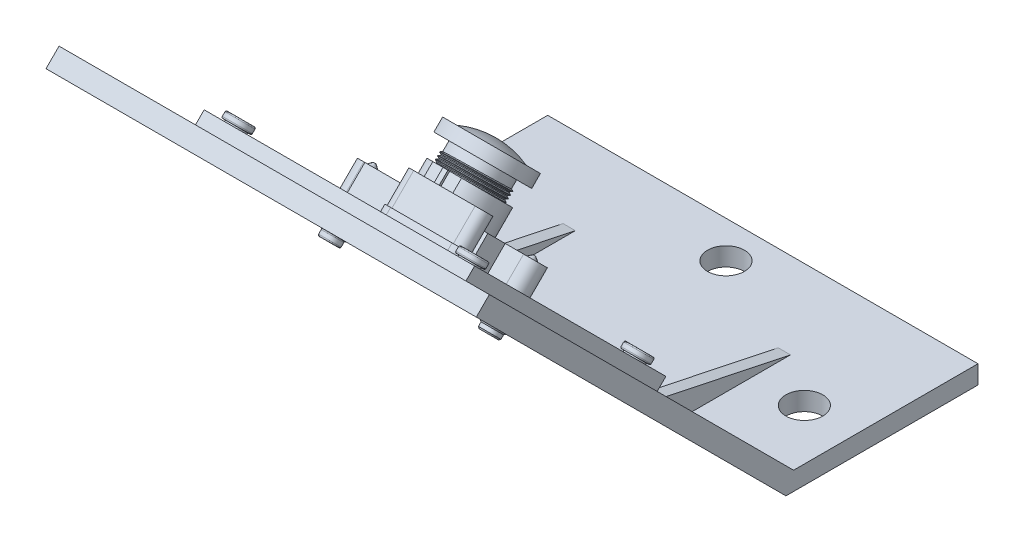
SolidWorks part; units mm, degrees
material "PF"
ref_plane "前视基准面" through (0, 0, 0) normal (0, 0, 1) x (1, 0, 0)
ref_plane "上视基准面" through (0, 0, 0) normal (0, 1, 0) x (1, 0, 0)
ref_plane "右视基准面" through (0, 0, 0) normal (1, 0, 0) x (0, 0, -1)
sketch "草图1" plane through (0, 0, 0) normal (1, 0, 0) x (0, 0, -1)
  line L0 (0, 0) -> (15, 0)
  line L1 (15, 0) -> (15, -1.5)
  line L2 (0, 0) -> (-24.7487, 24.7487)
  line L3 (15, -1.5) -> (-0.6213, -1.5)
  line L4 (-0.6213, -1.5) -> (-25.8094, 23.6881)
  line L5 (-25.8094, 23.6881) -> (-24.7487, 24.7487)
  dimension "D1" = 15
  dimension "D2" = 135
  dimension "D3" = 35
  dimension "D4" = 1.5
  dimension "D5" = 1.5
extrude "凸台-拉伸1" add sketch "草图1" along normal blind 35
ref_plane "基准面1" through (17.5, 0, 0) normal (1, 0, 0) x (0, 0, -1)
ref_plane "基准面2" through (26.25, 0, 0) normal (1, 0, 0) x (0, 0, -1)
sketch "草图2" plane through (26.25, 0, 0) normal (1, 0, 0) x (0, 0, -1)
  line L0 (8, 0) -> (-2.1213, 2.1213)
  line L1 (15, 0) -> (0, 0) construction
  line L2 (0, 0) -> (-24.7487, 24.7487) construction
  line L3 (-2.1213, 2.1213) -> (0, 0)
  line L4 (0, 0) -> (8, 0)
  dimension "D1" = 8
  dimension "D2" = 3
extrude "凸台-拉伸2" add sketch "草图2" along normal mid plane 1
mirror "镜向1" about plane through (17.5, 0, 0) normal (1, 0, 0) of "凸台-拉伸2"
sketch "草图3" plane through (0, 0, 0) normal (0, 1, 0) x (1, 0, 0)
  line L0 (17.5, 21.5668) -> (17.5, -38.1227) construction
  line L1 (8.25, 0) -> (0, 0) construction
  line L2 (4.125, 19.6823) -> (4.125, -36.0488) construction
  circle A0 centre (4.125, 5) radius 1.5
  dimension "D1" = 3
  dimension "D2" = 5
extrude "切除-拉伸1" cut sketch "草图3" against normal blind 50
mirror "镜向2" about plane through (17.5, 0, 0) normal (1, 0, 0) of "切除-拉伸1"
sketch "草图4" plane through (0, 0, 0) normal (0, 1, 0) x (1, 0, 0)
  line L0 (25.75, 0) -> (9.25, 0) construction
  circle A0 centre (17.5, 12) radius 1.5
  dimension "D1" = 3
  dimension "D2" = 12
extrude "切除-拉伸2" cut sketch "草图4" against normal blind 50
sketch "草图5" plane through (0, 0, 0) normal (0, 0.7071, -0.7071) x (1, 0, 0)
  line L0 (0, 0) -> (35, -35) construction
  line L1 (35, 0) -> (0, -35) construction
  line L3 (6.5, -6.5) -> (28.5, -6.5)
  line L4 (6.5, -6.5) -> (6.5, -28.5)
  line L5 (6.5, -28.5) -> (28.5, -28.5)
  line L6 (28.5, -6.5) -> (28.5, -28.5)
  line L7 (6.5, -6.5) -> (28.5, -28.5) construction
  line L8 (6.5, -28.5) -> (28.5, -6.5) construction
  point P8 (17.5, -17.5)
  point P10 (17.5, -17.5)
  dimension "D1" = 22
extrude "凸台-拉伸3" add sketch "草图5" along normal blind 1
sketch "草图6" plane through (0, 0.7071, -0.7071) normal (0, 0.7071, -0.7071) x (1, 0, 0)
  line L0 (6.5, -6.5) -> (28.5, -28.5) construction
  line L1 (28.5, -6.5) -> (6.5, -28.5) construction
  line L2 (-11.0984, -17.5) -> (63.4493, -17.5) construction
  line L3 (12.5, -14.5) -> (22.5, -14.5)
  line L4 (12.5, -14.5) -> (12.5, -16.5)
  line L5 (12.5, -20.5) -> (22.5, -20.5)
  line L6 (22.5, -14.5) -> (22.5, -16.5)
  line L7 (12.5, -14.5) -> (22.5, -20.5) construction
  line L8 (12.5, -20.5) -> (22.5, -14.5) construction
  line L10 (11, -16.5) -> (12.5, -16.5)
  line L11 (11, -18.5) -> (12.5, -18.5)
  line L12 (24, -18.5) -> (22.5, -18.5)
  line L13 (24, -16.5) -> (22.5, -16.5)
  line L14 (12.5, -18.5) -> (12.5, -20.5)
  line L15 (22.5, -18.5) -> (22.5, -20.5)
  arc A0 (11, -16.5) -> (11, -18.5) centre (11, -17.5) ccw
  arc A1 (24, -18.5) -> (24, -16.5) centre (24, -17.5) ccw
  point P8 (17.5, -17.5)
  point P10 (17.5, -17.5)
  dimension "D3" = 2
  dimension "D4" = 2
  dimension "D5" = 1.5
  dimension "D6" = 1.5
  dimension "D1" = 10
  dimension "D2" = 6
extrude "凸台-拉伸4" add sketch "草图6" along normal blind 2
sketch "草图7" plane through (0, 2.1213, -2.1213) normal (0, 0.7071, -0.7071) x (1, 0, 0)
  circle A0 centre (11, -17.5) radius 0.5
  circle A1 centre (24, -17.5) radius 0.5
  dimension "D1" = 1
  dimension "D2" = 1
extrude "切除-拉伸3" cut sketch "草图7" against normal blind 5
sketch "草图8" plane through (0, -1.0607, 1.0607) normal (0, -0.7071, 0.7071) x (1, 0, 0)
  circle A0 centre (11, 17.5) radius 0.75
  circle A1 centre (24, 17.5) radius 0.75
  dimension "D1" = 1.5
  dimension "D2" = 1.5
extrude "凸台-拉伸5" add sketch "草图8" along normal blind 0.5
sketch "草图9" plane through (0, -1.4142, 1.4142) normal (0, -0.7071, 0.7071) x (1, 0, 0)
  line L1 (10.5, 17.6) -> (11.5, 17.6)
  line L2 (10.5, 17.6) -> (10.5, 17.4)
  line L3 (10.5, 17.4) -> (11.5, 17.4)
  line L4 (11.5, 17.6) -> (11.5, 17.4)
  line L5 (10.5, 17.6) -> (11.5, 17.4) construction
  line L6 (10.5, 17.4) -> (11.5, 17.6) construction
  point P0 (11, 17.5)
  dimension "D1" = 1
  dimension "D2" = 0.2
extrude "切除-拉伸4" cut sketch "草图9" against normal blind 0.3
sketch "草图10" plane through (0, -1.4142, 1.4142) normal (0, -0.7071, 0.7071) x (1, 0, 0)
  line L1 (10.9, 18) -> (11.1, 18)
  line L2 (10.9, 18) -> (10.9, 17)
  line L3 (10.9, 17) -> (11.1, 17)
  line L4 (11.1, 18) -> (11.1, 17)
  line L5 (10.9, 18) -> (11.1, 17) construction
  line L6 (10.9, 17) -> (11.1, 18) construction
  point P0 (11, 17.5)
  dimension "D1" = 1
  dimension "D2" = 0.2
extrude "切除-拉伸5" cut sketch "草图10" against normal blind 0.3
mirror "镜向3" about plane through (17.5, 0, 0) normal (1, 0, 0) of "切除-拉伸4", "切除-拉伸5"
fillet "圆角1" radius 0.1 2 edges at (11, 11.844, 13.9654) (11, 10.4298, 13.2583)
chamfer "倒角1" distance 0.1 angle 45 2 edges at (24, 11.844, 13.9654) (24, 10.4298, 13.2583)
sketch "草图11" plane through (0, 2.1213, -2.1213) normal (0, 0.7071, -0.7071) x (1, 0, 0)
  point P0 (24, -17.5)
ref_plane "基准面3" through (0, 12.3744, 12.3744) normal (0, 0.7071, 0.7071) x (1, 0, 0)
sketch "草图12" plane through (0, 12.3744, 12.3744) normal (0, 0.7071, 0.7071) x (1, 0, 0)
  line L0 (24, 3.25) -> (24, -1.5)
  line L1 (35, -1.5) -> (0, -1.5) construction
  line L2 (24, -1.5) -> (24.7, -1.5)
  line L3 (24.7, -1.5) -> (24.4, 3.25)
  line L4 (24.4, 3.25) -> (24, 3.25)
  line L5 (22.5, 3) -> (24, 3) construction
  dimension "D1" = 0.25
  dimension "D2" = 0.4
  dimension "D3" = 0.7
revolve "旋转1" add sketch "草图12" angle 360 about L0
mirror "镜向4" about plane through (17.5, 0, 0) normal (1, 0, 0) of "旋转1"
chamfer "倒角2" distance 0.3 angle 45 2 edges at (24, 14.9553, 10.3591) (11, 14.9553, 10.3591) first distance on face at (24, 14.9553, 10.3591) first distance on face at (11, 14.9553, 10.3591)
sketch "草图13" plane through (0, 2.1213, -2.1213) normal (0, 0.7071, -0.7071) x (1, 0, 0)
  line L0 (-2.7876, -17.5) -> (40.9379, -17.5) construction
  line L1 (17.5, -1.488) -> (17.5, -14.65) construction
  line L2 (17.7, -14.9) -> (18.6673, -14.9)
  line L3 (16.3327, -14.9) -> (17.3, -14.9)
  line L4 (16.3327, -20.1) -> (17.3, -20.1)
  line L5 (17.5, -14.9) -> (17.5, -17.5) construction
  line L6 (17.5, -20.35) -> (17.5, -49.9835) construction
  line L8 (17.3, -14.9) -> (17.3, -14.7)
  line L9 (17.3, -14.7) -> (17.7, -14.7)
  line L10 (17.7, -14.9) -> (17.7, -14.7)
  line L11 (17.5, -14.9) -> (17.7, -14.7) construction
  line L12 (17.5, -19.9) -> (17.5, -20.1) construction
  line L13 (17.3, -20.3) -> (17.7, -20.3)
  line L14 (17.3, -20.3) -> (17.3, -20.1)
  line L16 (17.7, -20.3) -> (17.7, -20.1)
  line L19 (17.7, -20.1) -> (18.6673, -20.1)
  arc A0 (16.3327, -14.9) -> (16.3327, -20.1) centre (17.5, -17.5) ccw
  arc A1 (18.6673, -20.1) -> (18.6673, -14.9) centre (17.5, -17.5) ccw
  point P5 (17.5, -17.5)
  dimension "D1" = 5.7
  dimension "D2" = 2.6
  dimension "D3" = 2.6
  dimension "D4" = 0.4
  dimension "D5" = 0.2
  dimension "D7" = 0.2
extrude "凸台-拉伸6" add sketch "草图13" along normal blind 2
sketch "草图14" plane through (0, 3.5355, -3.5355) normal (0, 0.7071, -0.7071) x (1, 0, 0)
  circle A0 centre (17.5, -17.5) radius 2.25
  dimension "D1" = 4.5
extrude "凸台-拉伸7" add sketch "草图14" along normal blind 1
thread "螺纹线1" pitch 0.25 method extrude profile "螺纹线轮廓1" start angle 0, offset 0, length 1, pitch 0.25, diameter 4.5
ref_plane "基准面4" through (15.25, 16.617, 8.1317) normal (0, 0.7071, 0.7071) x (-1, 0, 0)
sketch "螺纹线轮廓1" plane through (15.25, 16.617, 8.1317) normal (0, 0.7071, 0.7071) x (-1, 0, 0)
  line L0 (0, 0) -> (0, 0.25) construction
  line L1 (0, 0) -> (0.1353, 0.0781)
  line L2 (0.1353, 0.0781) -> (0.1353, 0.1094)
  line L3 (0.1353, 0.1094) -> (0, 0.1875)
  line L4 (0.1353, 0.0937) -> (0, 0.0937) construction
  line L11 (0, 0) -> (0, 0.1875)
  point P2 (0, 0)
  dimension "Pitch" = 0.25
  dimension "Profile_Angle" = 60
  dimension "Profile_Land" = 0.0312
  dimension "Profile_Height" = 0.1353
sketch "草图17" plane through (0, 4.2426, -4.2426) normal (0, 0.7071, -0.7071) x (1, 0, 0)
  circle A0 centre (17.5, -17.5) radius 2.25
  dimension "D1" = 4.5
extrude "凸台-拉伸8" add sketch "草图17" along normal blind 0.5
sketch "草图18" plane through (0, 4.5962, -4.5962) normal (0, 0.7071, -0.7071) x (1, 0, 0)
  circle A0 centre (17.5, -17.5) radius 3.25
  dimension "D1" = 6.5
extrude "凸台-拉伸9" add sketch "草图18" along normal blind 1
sketch "草图19" plane through (0, 5.3033, -5.3033) normal (0, 0.7071, -0.7071) x (1, 0, 0)
  circle A0 centre (17.5, -17.5) radius 2.25
  dimension "D1" = 4.5
extrude "切除-拉伸7" cut sketch "草图19" against normal blind 0.2
sketch "草图20" plane through (0, 12.3744, 12.3744) normal (0, 0.7071, 0.7071) x (1, 0, 0)
  line L0 (17.5, 8) -> (17.5, 7.5)
  line L1 (20.75, 7.5) -> (14.25, 7.5) construction
  line L2 (17.5, 8) -> (15.0038, 8)
  line L3 (15.2, 7.5) -> (17.5, 7.5)
  arc A0 (15.2, 7.5) -> (17.5, 8) centre (17.5, 2.46) cw
  dimension "D1" = 0.5
  dimension "D2" = 2.3
revolve "旋转2" add sketch "草图20" angle 360 about L0
sketch "草图21" plane through (0, 0.7071, -0.7071) normal (0, 0.7071, -0.7071) x (1, 0, 0)
  line L0 (28.5, -6.5) -> (6.5, -6.5) construction
  line L1 (6.5, -6.5) -> (6.5, -28.5) construction
  line L2 (28.5, -28.5) -> (28.5, -6.5) construction
  line L3 (6.5, -28.5) -> (28.5, -28.5) construction
  line L4 (28.5, -28.5) -> (28.5, -6.5) construction
  circle A0 centre (8, -27) radius 0.75
  circle A1 centre (8, -8) radius 0.75
  circle A2 centre (27, -8) radius 0.75
  circle A3 centre (27, -27) radius 0.75
  dimension "D1" = 1.5
  dimension "D2" = 1.5
  dimension "D3" = 1.5
  dimension "D4" = 1.5
  dimension "D5" = 1.5
  dimension "D6" = 1.5
  dimension "D7" = 1.5
  dimension "D8" = 1.5
  dimension "D9" = 1.5
extrude "凸台-拉伸10" add sketch "草图21" along normal blind 0.1
sketch "草图22" plane through (0, 0.7778, -0.7778) normal (0, 0.7071, -0.7071) x (1, 0, 0)
  circle A0 centre (8, -8) radius 1
  circle A1 centre (27, -8) radius 1
  circle A2 centre (27, -27) radius 1
  circle A3 centre (8, -27) radius 1
  dimension "D1" = 2
extrude "凸台-拉伸11" add sketch "草图22" along normal blind 0.5
sketch "草图23" plane through (0, 1.1314, -1.1314) normal (0, 0.7071, -0.7071) x (1, 0, 0)
  line L1 (7.25, -7.875) -> (8.75, -7.875)
  line L2 (7.25, -7.875) -> (7.25, -8.125)
  line L3 (7.25, -8.125) -> (8.75, -8.125)
  line L4 (8.75, -7.875) -> (8.75, -8.125)
  line L5 (7.25, -7.875) -> (8.75, -8.125) construction
  line L6 (7.25, -8.125) -> (8.75, -7.875) construction
  point P0 (8, -8)
  dimension "D1" = 1.5
  dimension "D2" = 0.25
extrude "切除-拉伸8" cut sketch "草图23" against normal blind 0.3
sketch "草图24" plane through (0, 1.1314, -1.1314) normal (0, 0.7071, -0.7071) x (1, 0, 0)
  line L1 (7.875, -7.25) -> (8.125, -7.25)
  line L2 (7.875, -7.25) -> (7.875, -8.75)
  line L3 (7.875, -8.75) -> (8.125, -8.75)
  line L4 (8.125, -7.25) -> (8.125, -8.75)
  line L5 (7.875, -7.25) -> (8.125, -8.75) construction
  line L6 (7.875, -8.75) -> (8.125, -7.25) construction
  point P0 (8, -8)
  dimension "D1" = 1.5
  dimension "D2" = 0.25
extrude "切除-拉伸9" cut sketch "草图24" against normal blind 0.3
pattern_circular "阵列(圆周)1" count 4 over 360 about axis through (17.5, 17.6777, 7.0711) along (0, -0.7071, 0.7071) of "切除-拉伸8", "切除-拉伸9" reverse direction yes
fillet "圆角2" radius 0.1 8 edges at (27, 20.5768, 19.0212) (27, 20.9304, 18.6676) (27, 7.1418, 5.5861) (27, 7.4953, 5.2326) (8, 7.1418, 5.5861) (8, 7.4953, 5.2326) (8, 20.5768, 19.0212) (8, 20.9304, 18.6676)
sketch "草图25" plane through (0, 0.7071, -0.7071) normal (0, 0.7071, -0.7071) x (1, 0, 0)
  line L0 (12.5, -20.5) -> (22.5, -20.5) construction
  line L1 (17, -22.25) -> (22, -22.25)
  line L2 (17, -22.25) -> (17, -20.75)
  line L3 (17, -20.75) -> (22, -20.75)
  line L4 (22, -22.25) -> (22, -20.75)
  line L5 (22.5, -20.5) -> (22.5, -18.5) construction
  dimension "D1" = 0.25
  dimension "D2" = 1.5
  dimension "D3" = 5
  dimension "D4" = 0.5
extrude "凸台-拉伸12" add sketch "草图25" along normal blind 3
sketch "草图26" plane through (0, 2.8284, -2.8284) normal (0, 0.7071, -0.7071) x (1, 0, 0)
  line L0 (17, -20.75) -> (17, -22.25) construction
  line L1 (22, -22.25) -> (22, -20.75) construction
  circle A0 centre (17, -21.5) radius 0.75
  circle A1 centre (22, -21.5) radius 0.75
extrude "凸台-拉伸13" add sketch "草图26" against normal up to next
sketch "草图27" plane through (0, 0.7071, -0.7071) normal (0, 0.7071, -0.7071) x (1, 0, 0)
  line L0 (17, -21.5) -> (22, -21.5) construction
  line L1 (17, -20.6) -> (22, -20.6)
  line L2 (17, -22.4) -> (22, -22.4)
  arc A0 (17, -20.6) -> (17, -22.4) centre (17, -21.5) ccw
  arc A1 (22, -22.4) -> (22, -20.6) centre (22, -21.5) ccw
  arc A2 (22, -22.25) -> (22, -20.75) centre (22, -21.5) ccw construction
  point P2 (19.5, -21.5)
  dimension "D1" = 0.15
extrude "凸台-拉伸14" add sketch "草图27" along normal blind 0.5
ref_plane "基准面5" through (17.5, 0, 0) normal (1, 0, 0) x (0, 0, -1)
